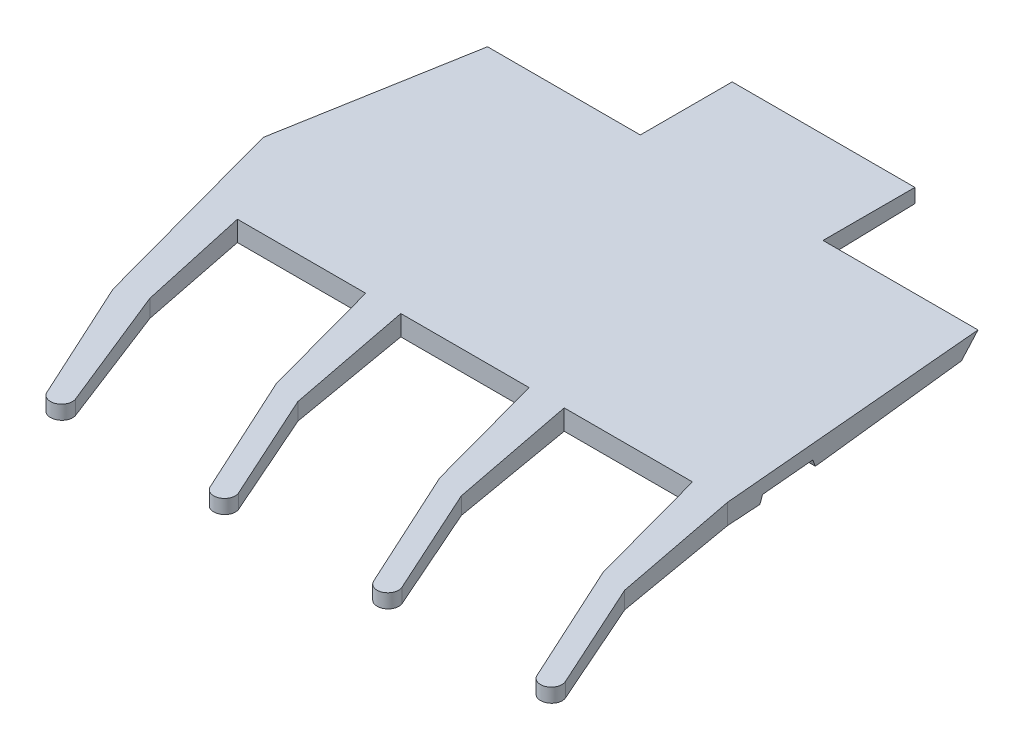
SolidWorks part; units mm, degrees
note: The reader was unsure of these and kept them because the rebuilt part matched: shared geometry of "Sketch4<2>".
ref_plane "Front Plane" through (0, 0, 0) normal (0, 0, 1) x (1, 0, 0)
ref_plane "Top Plane" through (0, 0, 0) normal (0, 1, 0) x (1, 0, 0)
ref_plane "Right Plane" through (0, 0, 0) normal (1, 0, 0) x (0, 0, -1)
sketch "Sketch1" plane through (0, 0, 0) normal (0, 1, 0) x (1, 0, 0)
  line L0 (-16, 0) -> (73.1571, 0) construction
  line L5 (0, 0) -> (0, 40.2216) construction
  line L27 (73.1571, -35.5613) -> (65.5205, -19.3479) construction
  line L30 (-16, 4.4715) -> (-16, -35.5613) construction
  line L60 (0, 40.2216) -> (0, -46.8609) construction
  line L62 (-16, 40.2216) -> (73.1571, 40.2216) construction
  line L63 (-16, 40.2216) -> (-16, -46.8609) construction
  line L64 (-16, -46.8609) -> (73.1571, -46.8609) construction
  line L65 (73.1571, 40.2216) -> (73.1571, -46.8609) construction
sketch "Sketch2" plane through (0, 0, 0) normal (1, 0, 0) x (0, 0, -1)
  line L0 (1.7835, -3.0087) -> (40.2478, -2.0043) construction
  line L1 (40.2216, 0) -> (40.2478, -2.0043) construction
  line L2 (40.2216, 0) -> (-46.8609, 0) construction
  line L7 (-6.8614, -3.0072) -> (-46.8613, -2) construction
  line L8 (-6.8614, -3.0072) -> (-6.4481, -2.0072) construction
  line L9 (1.3705, -2.0086) -> (-6.4481, -2.0072) construction
  line L10 (1.3705, -2.0086) -> (1.7835, -3.0087) construction
  line L11 (1.7835, -3.0087) -> (40.2478, -2.0043)
  line L12 (40.2216, 0) -> (40.2478, -2.0043)
  line L13 (40.2216, 0) -> (-48.2326, 0)
  line L14 (-48.2326, 0) -> (-48.2326, -1.9655)
  line L18 (-6.8614, -3.0072) -> (-48.2326, -1.9655)
  line L19 (-6.8614, -3.0072) -> (-6.4481, -2.0072)
  line L20 (1.3705, -2.0086) -> (-6.4481, -2.0072)
  line L21 (1.3705, -2.0086) -> (1.7835, -3.0087)
  line L22 (39.2194, -1.0154) -> (-46.8611, -1) construction
  line L23 (39.2194, -1.0154) -> (-48.2326, -0.9998) construction
extrude "Boss-Extrude1" add sketch "Sketch2" along normal up to vertex (73.1571 mm away) from vertex at -16 starting at point (-16, 0, 46.8609)
sketch "Sketch3" plane through (0, 0, 0) normal (0, 1, 0) x (1, 0, 0)
  line L0 (-16, 0) -> (-7.9928, -29.3622) construction
  line L1 (-7.9928, -29.3622) -> (0.6836, -48.2326) construction
  line L2 (0.6836, -48.2326) -> (3.4026, -46.8609) construction
  line L3 (3.4026, -46.8609) -> (-4.234, -27.882) construction
  line L4 (-4.234, -27.882) -> (-7.7545, -11.9012) construction
  line L5 (-7.7545, -11.9012) -> (10.497, -11.9012) construction
  line L6 (10.497, -11.9012) -> (15.2587, -29.3622) construction
  line L7 (15.2587, -29.3622) -> (23.9351, -48.2326) construction
  line L8 (23.9351, -48.2326) -> (26.6541, -46.8609) construction
  line L9 (26.6541, -46.8609) -> (19.0175, -30.0669) construction
  line L10 (19.0175, -30.0669) -> (15.497, -11.9012) construction
  line L11 (33.7485, -11.9012) -> (15.497, -11.9012) construction
  line L12 (33.7485, -11.9012) -> (38.5102, -29.3622) construction
  line L13 (38.5102, -29.3622) -> (47.1866, -48.2326) construction
  line L14 (47.1866, -48.2326) -> (49.9056, -46.8609) construction
  line L15 (49.9056, -46.8609) -> (42.269, -30.0669) construction
  line L16 (42.269, -30.0669) -> (38.7485, -11.9012) construction
  line L17 (38.7485, -11.9012) -> (57, -11.9012) construction
  line L18 (57, -11.9012) -> (61.7617, -29.3622) construction
  line L19 (61.7617, -29.3622) -> (70.4381, -48.2326) construction
  line L20 (70.4381, -48.2326) -> (73.1571, -46.8609) construction
  line L21 (73.1571, -46.8609) -> (65.5205, -30.0669) construction
  line L22 (65.5205, -30.0669) -> (62, -11.9012) construction
  line L23 (-16, 0) -> (-7.9928, -29.3622)
  line L24 (-7.9928, -29.3622) -> (0.6836, -48.2326) construction
  line L25 (0.6836, -48.2326) -> (3.4026, -46.8609) construction
  line L26 (3.4026, -46.8609) -> (-4.234, -27.882) construction
  line L27 (-4.234, -27.882) -> (-7.7545, -11.9012)
  line L28 (-7.7545, -11.9012) -> (10.497, -11.9012)
  line L29 (10.497, -11.9012) -> (15.2587, -29.3622)
  line L30 (15.2587, -29.3622) -> (23.9351, -48.2326) construction
  line L31 (23.9351, -48.2326) -> (26.6541, -46.8609) construction
  line L32 (26.6541, -46.8609) -> (19.0175, -30.0669) construction
  line L33 (19.0175, -30.0669) -> (15.497, -11.9012)
  line L34 (33.7485, -11.9012) -> (15.497, -11.9012)
  line L35 (33.7485, -11.9012) -> (38.5102, -29.3622)
  line L36 (38.5102, -29.3622) -> (47.1866, -48.2326) construction
  line L37 (47.1866, -48.2326) -> (49.9056, -46.8609) construction
  line L38 (49.9056, -46.8609) -> (42.269, -30.0669) construction
  line L39 (42.269, -30.0669) -> (38.7485, -11.9012)
  line L40 (38.7485, -11.9012) -> (57, -11.9012)
  line L41 (57, -11.9012) -> (61.7617, -29.3622)
  line L42 (61.7617, -29.3622) -> (70.4381, -48.2326) construction
  line L43 (70.4381, -48.2326) -> (73.1571, -46.8609) construction
  line L44 (73.1571, -46.8609) -> (65.5205, -30.0669) construction
  line L45 (65.5205, -30.0669) -> (62, -11.9012)
  line L46 (-16, 0) -> (-8.9078, 40.2216)
  line L47 (-8.9078, 40.2216) -> (57.4398, 40.2216)
  line L48 (57.4398, 40.2216) -> (62, -11.9012)
  line L49 (-16, 40.2216) -> (73.1571, 40.2216) construction
  line L50 (0.0091, -46.7655) -> (-7.9928, -29.3622)
  line L51 (-4.234, -27.882) -> (2.8685, -45.5337)
  line L52 (23.2746, -46.7961) -> (15.2587, -29.3622)
  line L53 (19.0175, -30.0669) -> (26.048, -45.528)
  line L54 (38.5102, -29.3622) -> (46.5261, -46.7961)
  line L55 (49.2995, -45.528) -> (42.269, -30.0669)
  line L56 (61.7617, -29.3622) -> (69.7776, -46.7961)
  line L57 (72.5509, -45.528) -> (65.5205, -30.0669)
  arc A0 (72.5509, -45.528) -> (69.7776, -46.7961) centre (71.163, -46.1591) cw
  arc A1 (49.2995, -45.528) -> (46.5261, -46.7961) centre (47.9115, -46.1591) cw
  arc A2 (26.048, -45.528) -> (23.2746, -46.7961) centre (24.66, -46.1591) cw
  arc A3 (2.8685, -45.5337) -> (0.0091, -46.7655) centre (1.4239, -46.115) cw
  dimension "D1" = 100
  dimension "D2" = 95
extrude "Cut-Extrude1" cut sketch "Sketch3" against normal through all flip side to cut
sketch "Sketch4" plane through (0, 0, 0) normal (1, 0, 0) x (0, 0, -1)
  line L0 (8.0837, -18.2637) -> (31.7788, 3.9296) construction
  line L1 (8.0837, -18.2637) -> (31.7788, 3.9296) construction
  line L2 (24.5674, -2.4138) -> (27.1445, 0)
  line L3 (27.1445, 0) -> (40.2216, 0)
  line L4 (40.2216, 0) -> (40.2478, -2.0043)
  line L5 (40.2478, -2.0043) -> (24.5674, -2.4138)
  line L8 (40.2216, 0) -> (40.2478, -2.0043) construction
  line L9 (40.2216, 0) -> (-46.8609, 0) construction
  line L10 (1.7835, -3.0087) -> (40.2478, -2.0043) construction
  dimension "D1" = 0.3
extrude "Cut-Extrude2" cut sketch "Sketch4" against normal through all from vertex at 10.5292
extrude "Cut-Extrude3" cut sketch "Sketch4<2>" along normal through all from vertex at 36.5292
sketch "Sketch4<2>" plane through (0, 0, 0) normal (1, 0, 0) x (0, 0, -1) same geometry as "Sketch4"
